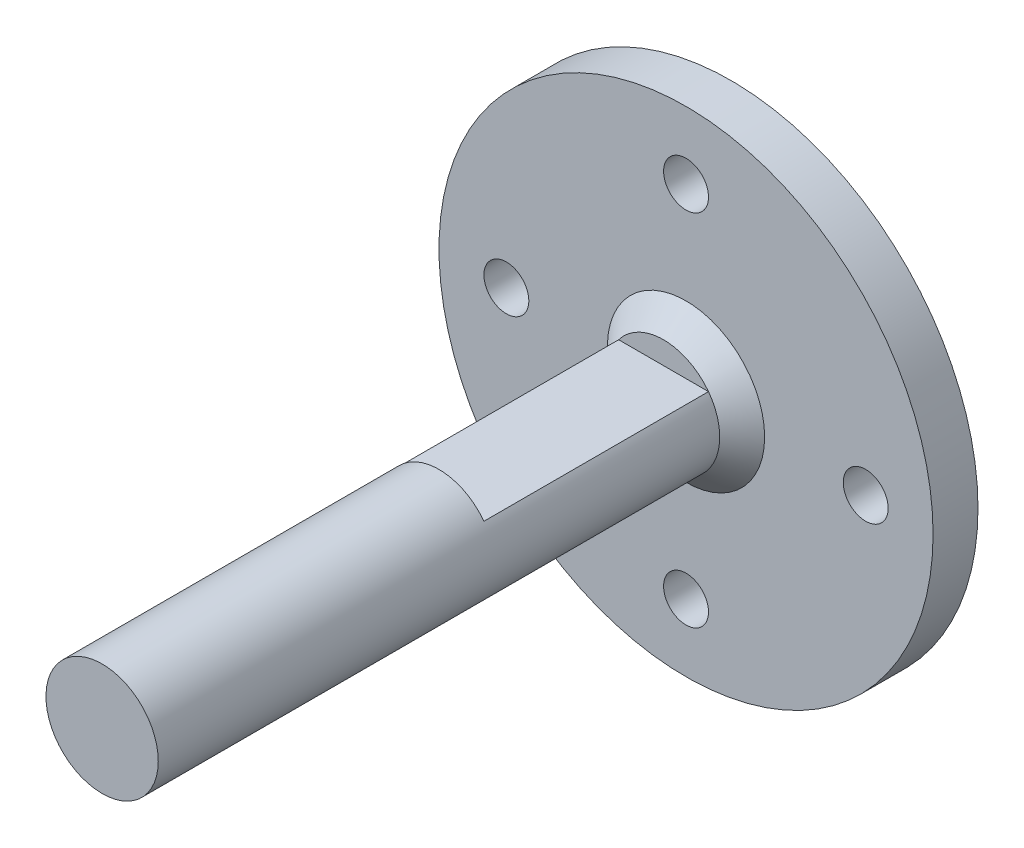
SolidWorks part; units mm, degrees
other "Uwaga1"
sketch "Szkic4" plane through (11, 11, 28) normal (0.6275, 0.305, 0.7164) x (0.6868, 0.2167, -0.6938)
material "Chromowa stal nierdzewna"
ref_plane "Płaszczyzna przednia" through (0, 0, 0) normal (0, 0, 1) x (1, 0, 0)
ref_plane "Płaszczyzna górna" through (0, 0, 0) normal (0, 1, 0) x (1, 0, 0)
ref_plane "Płaszczyzna prawa" through (0, 0, 0) normal (1, 0, 0) x (0, 0, -1)
sketch "Szkic1" plane through (0, 0, 0) normal (0, 0, 1) x (1, 0, 0)
  circle A0 centre (0, 0) radius 11
  circle A1 centre (0, 8) radius 1
  circle A2 centre (8, 0) radius 1
  circle A3 centre (0, -8) radius 1
  circle A4 centre (-8, 0) radius 1
  point P14 (0, 0)
  dimension "D1" = 22
  dimension "D2" = 2
  dimension "D3" = 8
  dimension "D4" = 4
extrude "Dodanie-wyciągnięcie1" add sketch "Szkic1" along normal blind 2
sketch "Szkic2" plane through (0, 0, 2) normal (0, 0, 1) x (1, 0, 0)
  circle A0 centre (0, 0) radius 2.5
  dimension "D1" = 5
extrude "Dodanie-wyciągnięcie2" add sketch "Szkic2" along normal blind 26
sketch "Szkic3" plane through (0, 0, 28) normal (0, 0, 1) x (1, 0, 0)
  line L1 (2, 1.5) -> (-2, 1.5)
  arc A0 (2, 1.5) -> (-2, 1.5) centre (0, 0) ccw
extrude "Wytnij-wyciągnięcie1" cut sketch "Szkic3" against normal blind 10 from offset 15 offset against normal yes
chamfer "Sfazowanie1" distance 1 angle 45 1 edges at (2.5, 0, 2)
